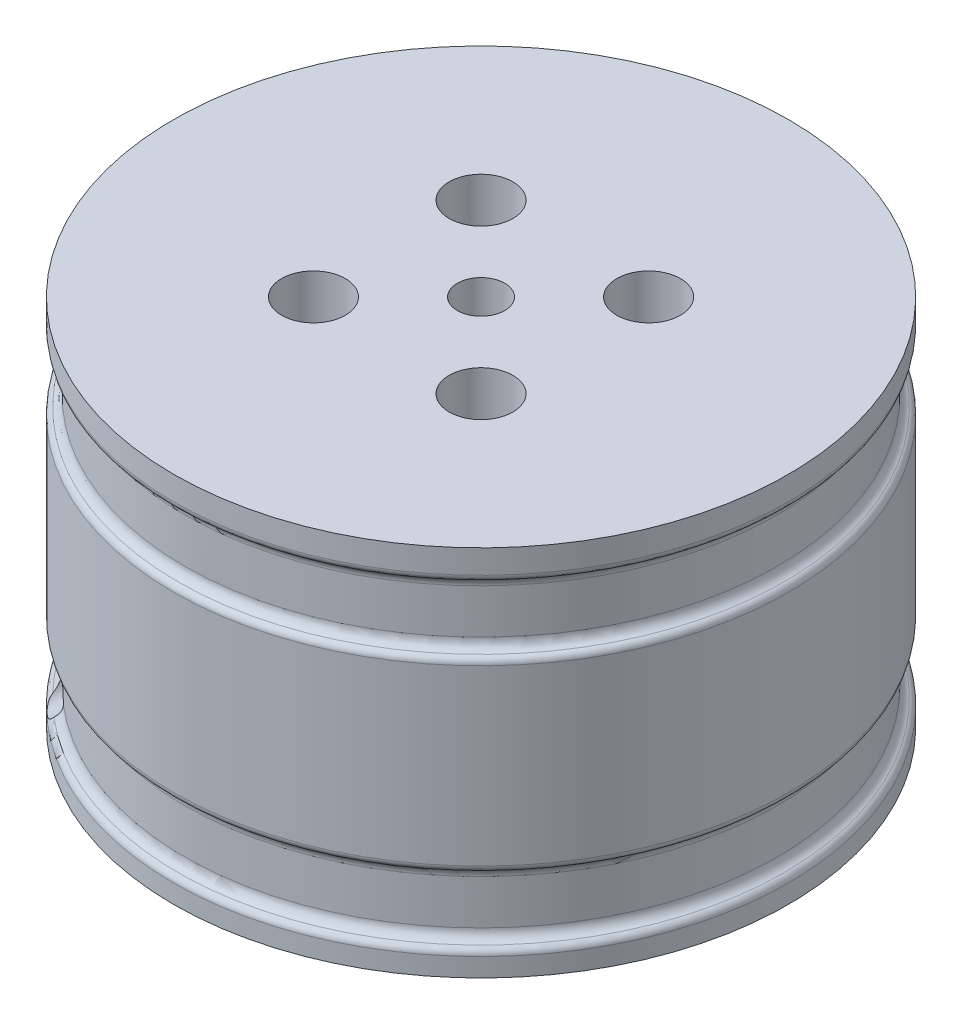
SolidWorks part; units mm, degrees
note: The reader was unsure of these and kept them because the rebuilt part matched: shared geometry of "Sketch1<3>", "Sketch1<4>", "Sketch1<5>", "Sketch3<4>".
other "Markup1"
sketch "Sketch4" plane through (20.75, 18.15, -20.75) normal (0.2314, 0.6334, -0.7384) x (-0.1781, -0.7186, -0.6722)
ref_plane "Front Plane" through (0, 0, 0) normal (0, 0, 1) x (1, 0, 0)
ref_plane "Top Plane" through (0, 0, 0) normal (0, 1, 0) x (1, 0, 0)
ref_plane "Right Plane" through (0, 0, 0) normal (1, 0, 0) x (0, 0, -1)
sketch "Sketch1" plane through (0, 0, 0) normal (0, 1, 0) x (1, 0, 0)
  line L8 (-5.6569, 5.6569) -> (5.6569, -5.6569) construction
  line L9 (5.6569, 5.6569) -> (-5.6569, -5.6569) construction
  line L10 (-5.6569, 5.6569) -> (-5.6569, -5.6569) construction
  line L11 (-5.6569, 5.6569) -> (5.6569, 5.6569) construction
  circle A4 centre (0, 0) radius 20
  circle A9 centre (0, 0) radius 1.6
  circle A10 centre (0, 0) radius 10
  circle A11 centre (0, 0) radius 8 construction
  circle A12 centre (5.6569, 5.6569) radius 1.2
  circle A13 centre (5.6569, -5.6569) radius 1.2
  circle A14 centre (-5.6569, -5.6569) radius 1.2
  circle A15 centre (-5.6569, 5.6569) radius 1.2
  circle A16 centre (0, 0) radius 4.2
  point P11 (0, 0)
  point P13 (0, 0)
  dimension "D1" = 40
  dimension "D3" = 3.2
  dimension "D2" = 20
  dimension "D4" = 2.4
  dimension "D5" = 16
  dimension "D6" = 8.4
extrude "Boss-Extrude1" add sketch "Sketch1" along normal blind 18.15
extrude "Boss-Extrude2" add sketch "Sketch1<3>" against normal blind 7
sketch "Sketch1<3>" plane through (0, 0, 0) normal (0, 1, 0) x (1, 0, 0) same geometry as "Sketch1"
extrude "Cut-Extrude2" cut sketch "Sketch1<4>" along normal blind 1 from surface contours A10 A16 A15 A14 A13 A12 | A16 A9
sketch "Sketch1<4>" plane through (0, 0, 0) normal (0, 1, 0) x (1, 0, 0) same geometry as "Sketch1"
extrude "Cut-Extrude3" cut sketch "Sketch1<5>" along normal blind 7 from surface at -7 contours A16 A9 starting at face at (0, -7, 20)
sketch "Sketch1<5>" plane through (0, 0, 0) normal (0, 1, 0) x (1, 0, 0) same geometry as "Sketch1"
sketch "Sketch8" plane through (0, 0, 0) normal (0, 1, 0) x (1, 0, 0)
  circle A0 centre (5.6569, 5.6569) radius 2.15
  circle A1 centre (5.6569, -5.6569) radius 2.15
  circle A2 centre (-5.6569, -5.6569) radius 2.15
  circle A3 centre (-5.6569, 5.6569) radius 2.15
  circle A4 centre (-5.6569, -5.6569) radius 1.2 construction
  dimension "D1" = 4.3
extrude "Cut-Extrude4" cut sketch "Sketch8" against normal offset from surface (10.15 mm away) 14 from surface at 18.15 up to face at (-5.6569, -6, -4.4569) starting at face at (0, 18.15, 20)
sketch "Sketch2" plane through (0, 0, 0) normal (0, 0, 1) x (1, 0, 0)
  line L0 (20.75, 11.65) -> (20.75, -0.85)
  line L1 (20, -7) -> (20, 18.15)
  line L4 (20.75, -5.35) -> (20.75, -7)
  line L5 (20.75, -7) -> (20, -7)
  line L6 (0, 0) -> (0, -7.4892) construction
  line L7 (20, 18.15) -> (20.75, 18.15)
  line L8 (20.75, 18.15) -> (20.75, 16.15)
  line L9 (-20, -7) -> (20, -7) construction
  arc A2 (20.75, 16.15) -> (20, 15.4) centre (20.75, 15.4) ccw
  arc A3 (20.75, -5.35) -> (20, -4.6) centre (20.75, -4.6) cw
  arc A4 (20.75, -0.85) -> (20, -1.6) centre (20.75, -1.6) ccw
  arc A5 (20.75, 11.65) -> (20, 12.4) centre (20.75, 12.4) cw
  dimension "D1" = 21.5
  dimension "D4" = 3
  dimension "D2" = 0.75
  dimension "D3" = 1.65
  dimension "D5" = 2
  dimension "D6" = 20
  dimension "D7" = 3
revolve "Revolve1" add sketch "Sketch2" angle 360 about L6
fillet "Fillet1" radius 0.5 4 edges at (0, 16.15, 20.75) (0, 11.65, 20.75) (0, -0.85, 20.75) (0, -5.35, 20.75)
sketch "Sketch3" plane through (0, 0, 0) normal (0, 0, 1) x (1, 0, 0)
  line L0 (-14, -4.6) -> (24.4966, -4.6) construction
  circle A0 centre (-14, -4.6) radius 1
  circle A1 centre (-14, 15.4) radius 1
  circle A2 centre (-14, -4.6) radius 2
  circle A3 centre (-14, 15.4) radius 2
  dimension "D1" = 2
  dimension "D3" = 20
  dimension "D5" = 4
  dimension "D2" = 4.6
  dimension "D4" = 14
extrude "Cut-Extrude1" cut sketch "Sketch3" against normal through all both and the other way through all contours A0 | A1
extrude "Cut-Extrude5" cut sketch "Sketch3<4>" against normal blind 10 from offset 9 offset against normal yes
sketch "Sketch3<4>" plane through (0, 0, 0) normal (0, 0, 1) x (1, 0, 0) same geometry as "Sketch3"
